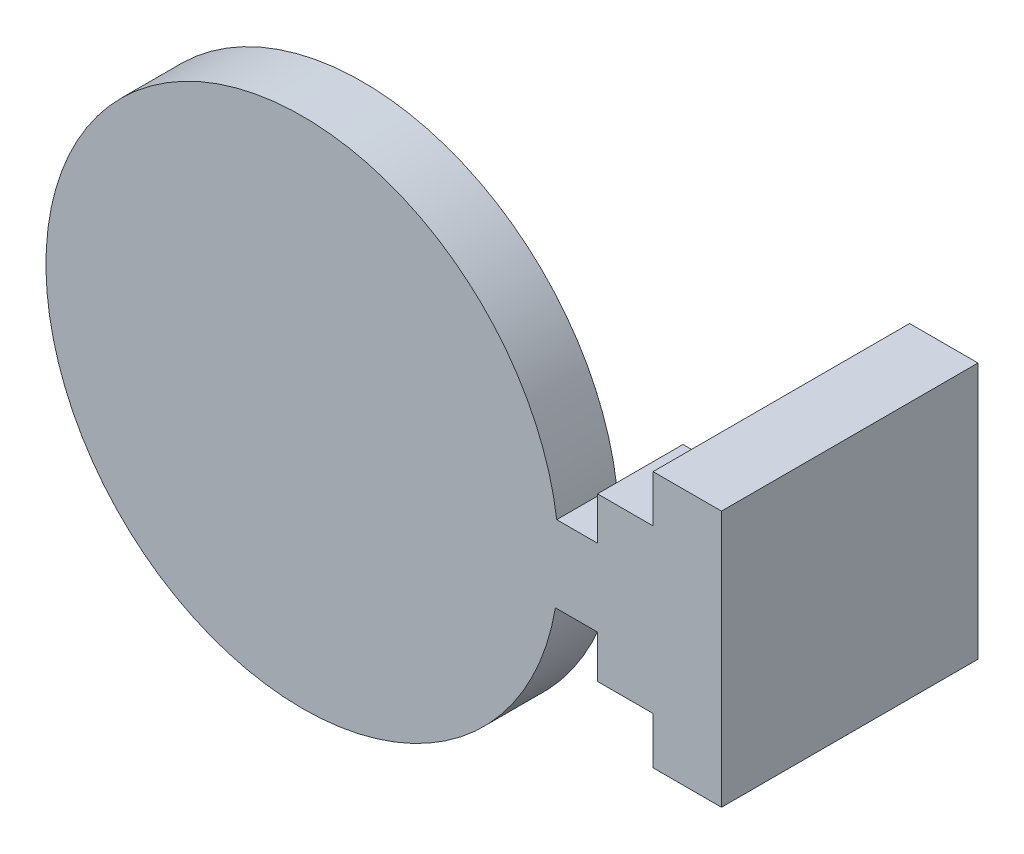
SolidWorks part; units mm, degrees
ref_plane "前基準面" through (0, 0, 0) normal (0, 0, 1) x (1, 0, 0)
ref_plane "上基準面" through (0, 0, 0) normal (0, 1, 0) x (1, 0, 0)
ref_plane "右基準面" through (0, 0, 0) normal (1, 0, 0) x (0, 0, -1)
ref_axis "基準軸1" through (0, -55, 0) along (0, 1, 0)
ref_axis "基準軸2" through (-88.99, 0, 0) along (1, 0, 0)
ref_axis "基準軸3" through (0, 0, 55) along (0, 0, -1)
sketch "草圖1" plane through (0, 0, 0) normal (1, 0, 0) x (0, 0, -1)
  line L1 (0, 0) -> (10, 0)
  line L2 (0, 0) -> (0, 19)
  line L3 (0, 19) -> (10, 19)
  line L4 (10, 0) -> (10, 19)
  dimension "D1" = 19
  dimension "D2" = 10
extrude "填料-伸長1" add sketch "草圖1" against normal blind 6.5
sketch "草圖2" plane through (0, 0, 0) normal (0, 0, 1) x (1, 0, 0)
  line L0 (0, -55) -> (0, 55) construction
  line L1 (55, 0) -> (-55, 0) construction
  line L2 (-11.2679, 14) -> (-6.5, 14)
  line L3 (-6.5, 19) -> (-6.5, 0) construction
  line L4 (-11.4196, 5) -> (-6.5, 5)
  line L5 (-88.99, 0) -> (88.99, 0) construction
  line L6 (-6.5, 19) -> (0, 19) construction
  line L7 (-6.5, 5) -> (-6.5, 14)
  arc A0 (-11.2679, 14) -> (-11.4196, 5) centre (-41, 10) ccw
  dimension "D1" = 60
  dimension "D2" = 41
  dimension "D3" = 10
  dimension "D4" = 5
  dimension "D5" = 5
extrude "填料-伸長2" add sketch "草圖2" against normal blind 7
fillet "圓角1" radius 3 1 edges at (-6.5, 9.5, -7)
sketch "草圖3" plane through (0, 0, 0) normal (1, 0, 0) x (0, 0, -1)
  line L1 (0, -5.5) -> (30, -5.5)
  line L2 (0, -5.5) -> (0, 24.5)
  line L3 (0, 24.5) -> (30, 24.5)
  line L4 (30, -5.5) -> (30, 24.5)
  line L5 (-55, 0) -> (55, 0) construction
  line L7 (0, -55) -> (0, 55) construction
  dimension "D1" = 30
  dimension "D2" = 30
  dimension "D3" = 24.5
extrude "填料-伸長3" add sketch "草圖3" along normal blind 8
sketch "草圖4" plane through (0, 0, -30) normal (0, 0, -1) x (-1, 0, 0)
  line L1 (-6.5, 15.2189) -> (-6.5, 11.2186)
  line L2 (-8, -5.5) -> (-8, 24.5) construction
  dimension "D1" = 1.5
